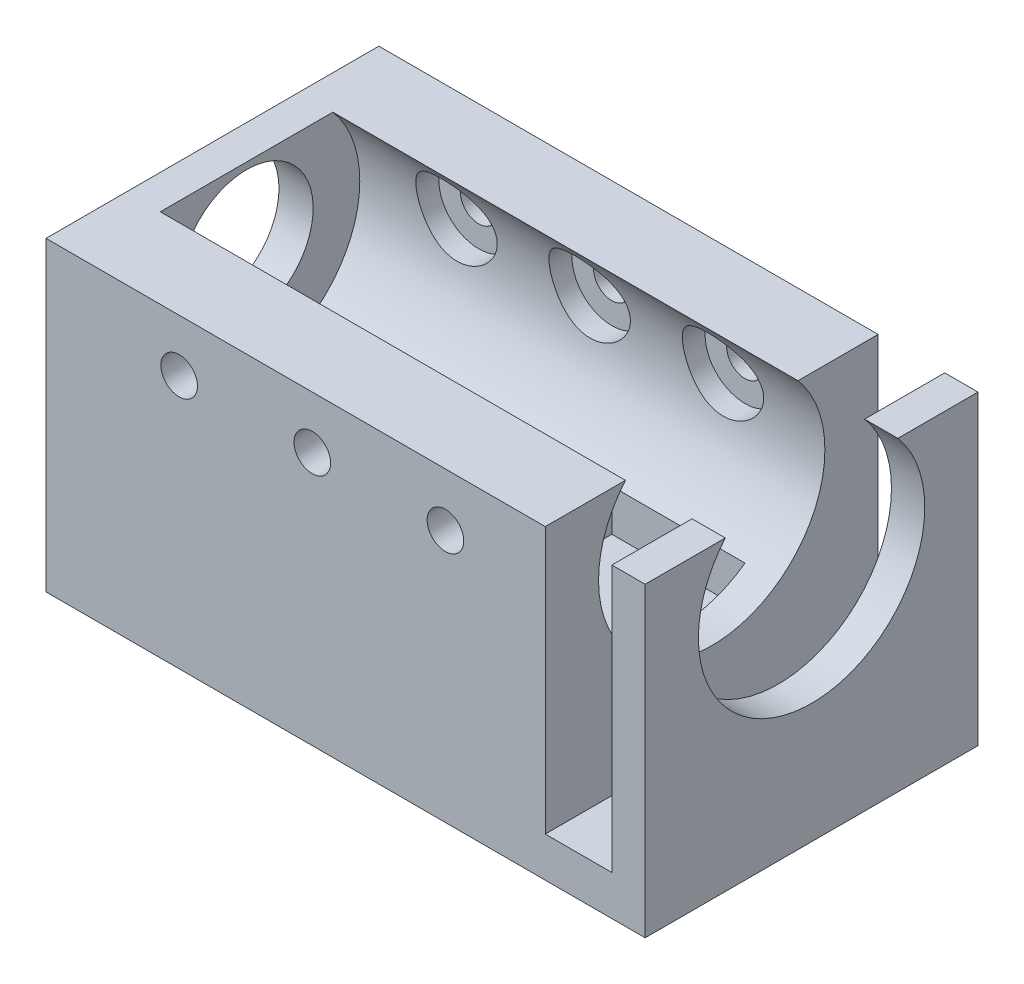
SolidWorks part; units mm, degrees
ref_plane "Front Plane" through (0, 0, 0) normal (0, 0, 1) x (1, 0, 0)
ref_plane "Top Plane" through (0, 0, 0) normal (0, 1, 0) x (1, 0, 0)
ref_plane "Right Plane" through (0, 0, 0) normal (1, 0, 0) x (0, 0, -1)
sketch "Sketch1" plane through (0, 0, 0) normal (0, 0, 1) x (1, 0, 0)
  line L1 (-76.2, -69.85) -> (38.1, -69.85)
  line L2 (-76.2, -69.85) -> (-76.2, 0)
  line L3 (-76.2, 0) -> (38.1, 0)
  line L4 (38.1, -69.85) -> (38.1, 0)
  line L5 (-76.2, -69.85) -> (38.1, 0) construction
  line L6 (-76.2, 0) -> (38.1, -69.85) construction
  point P0 (0, 0)
  dimension "D1" = 114.3
  dimension "D2" = 69.85
  dimension "D3" = 38.1
extrude "Boss-Extrude1" add sketch "Sketch1" along normal mid plane 63.5
sketch "Sketch10" plane through (0, -69.85, 0) normal (0, -1, 0) x (1, 0, 0)
  line L1 (-12.7, -12.7) -> (12.7, -12.7)
  line L2 (-12.7, -12.7) -> (-12.7, 12.7)
  line L3 (-12.7, 12.7) -> (12.7, 12.7)
  line L4 (12.7, -12.7) -> (12.7, 12.7)
  line L5 (-12.7, -12.7) -> (12.7, 12.7) construction
  line L6 (-12.7, 12.7) -> (12.7, -12.7) construction
  point P0 (0, 0)
  dimension "D1" = 25.4
  dimension "D2" = 25.4
extrude "Cut-Extrude6" cut sketch "Sketch10" along normal blind 50.8 from surface starting at face at (-19.05, 0, 0)
sketch "Sketch2" plane through (0, 0, 0) normal (0, 0, 1) x (1, 0, 0)
  line L0 (-152.4829, -25.4) -> (0, -25.4) construction
  line L1 (-69.6809, -3.81) -> (-69.6809, -12.7)
  line L2 (38.1, 0) -> (-76.2, 0) construction
  line L3 (38.1, 0) -> (-76.2, 0) construction
  line L5 (-32, -25.4) -> (-32, -3.81) construction
  line L6 (-128.4172, -25.4) -> (-157.8092, -25.4)
  line L7 (0, -25.4) -> (122.0995, -25.4)
  line L8 (-607.3619, -25.4) -> (0, -25.4) construction
  line L9 (-69.6809, -3.81) -> (0, -3.81)
  line L10 (0, -25.4) -> (-128.4172, -25.4)
  line L12 (122.0995, -25.4) -> (122.0995, -3.81)
  line L13 (0, -3.81) -> (0, -25.4) construction
  line L14 (-69.6809, -12.7) -> (-220.2024, -12.7)
  line L15 (-220.2024, -12.7) -> (-220.2024, -25.4)
  line L16 (-220.2024, -25.4) -> (-157.8092, -25.4)
  line L17 (122.0995, -3.81) -> (0, -3.81)
  point P3 (0, 0)
  point P5 (-68.8502, -6.366)
  point P23 (-32, -25.4)
  dimension "D1" = 21.59
  dimension "D2" = 37.6809
  dimension "D3" = 25.4
  dimension "D4" = 32
  dimension "D9" = 12.7
revolve "Cut-Revolve1" cut sketch "Sketch2" angle 360 about L0
sketch "Sketch30" plane through (38.1, 0, 0) normal (1, 0, 0) x (0, 0, -1)
  line L0 (-31.75, 0) -> (31.75, 0) construction
  line L1 (-31.75, 0) -> (31.75, 0)
  line L2 (-31.75, 0) -> (-31.75, -11.43)
  line L3 (-31.75, -11.43) -> (31.75, -11.43)
  line L4 (31.75, 0) -> (31.75, -11.43)
  line L5 (-31.75, -69.85) -> (-31.75, 0) construction
  point P6 (0, 0)
  dimension "D2" = 11.43
extrude "Cut-Extrude25" cut sketch "Sketch30" against normal through all
sketch "Sketch31" plane through (0, 0, 31.75) normal (0, 0, 1) x (1, 0, 0)
  line L0 (-76.2, -11.43) -> (-76.2, -69.85) construction
  circle A0 centre (-50.8, -21.4227) radius 3.4925
  circle A1 centre (-25.4, -21.4227) radius 3.4925
  circle A2 centre (0, -21.59) radius 3.4925
  dimension "D2" = 6.985
  dimension "D1" = 21.59
  dimension "D3" = 25.4
  dimension "D4" = 25.4
  dimension "D5" = 25.4
extrude "Cut-Extrude26" cut sketch "Sketch31" against normal through all
sketch "Sketch32" plane through (0, 0, 0) normal (0, 0, 1) x (1, 0, 0)
  circle A0 centre (-50.8, -21.4227) radius 7.62
  circle A1 centre (-25.4, -21.4227) radius 7.62
  circle A2 centre (0, -21.59) radius 7.62
  dimension "D1" = 15.24
extrude "Cut-Extrude27" cut sketch "Sketch32" against normal blind 25.4 and the other way blind 25.4
sketch "Sketch33" plane through (0, -11.43, 0) normal (0, 1, 0) x (1, 0, 0)
  line L0 (-76.2, 31.75) -> (38.1, 31.75) construction
  line L1 (19.05, 31.75) -> (31.75, 31.75)
  line L2 (19.05, 31.75) -> (19.05, -31.75)
  line L3 (19.05, -31.75) -> (31.75, -31.75)
  line L4 (31.75, 31.75) -> (31.75, -31.75)
  line L5 (-76.2, -31.75) -> (38.1, -31.75) construction
  line L6 (38.1, 16.4611) -> (38.1, 31.75) construction
  dimension "D1" = 12.7
  dimension "D2" = 6.35
extrude "Cut-Extrude28" cut sketch "Sketch33" against normal blind 50.8
